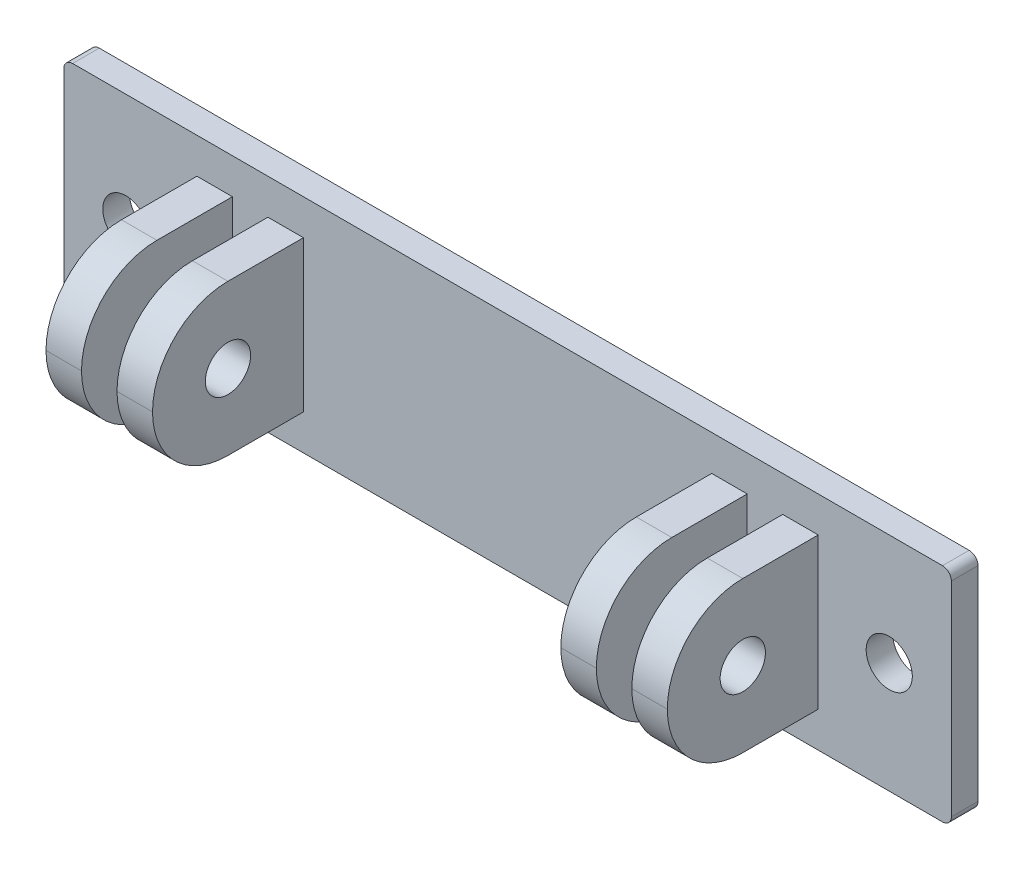
SolidWorks part; units mm, degrees
ref_plane "Ebene vorne" through (0, 0, 0) normal (0, 0, 1) x (1, 0, 0)
ref_plane "Ebene oben" through (0, 0, 0) normal (0, 1, 0) x (1, 0, 0)
ref_plane "Ebene rechts" through (0, 0, 0) normal (1, 0, 0) x (0, 0, -1)
sketch "Skizze1" plane through (0, 0, 0) normal (0, 0, 1) x (1, 0, 0)
  line L1 (95.9477, 18.6427) -> (-4.0523, 18.6427)
  line L2 (95.9477, 18.6427) -> (95.9477, -6.3573)
  line L3 (95.9477, -6.3573) -> (-4.0523, -6.3573)
  line L4 (-4.0523, 18.6427) -> (-4.0523, -6.3573)
  point P4 (-4.0523, -6.3573)
  dimension "D1" = 100
  dimension "D2" = 25
extrude "Aufsatz-Linear austragen1" add sketch "Skizze1" along normal blind 3 contours L2 L1 L4 L3
sketch "Skizze3" plane through (0, 0, 3) normal (0, 0, 1) x (1, 0, 0)
  line L1 (14.9477, 14.6427) -> (10.9477, 14.6427)
  line L2 (14.9477, 14.6427) -> (14.9477, -2.3573)
  line L3 (14.9477, -2.3573) -> (10.9477, -2.3573)
  line L4 (10.9477, 14.6427) -> (10.9477, -2.3573)
  line L6 (-42.759, -2.3573) -> (-24.1476, -2.3573) construction
  line L7 (18.9477, 14.6427) -> (22.9477, 14.6427)
  line L8 (18.9477, 14.6427) -> (18.9477, -2.3573)
  line L9 (18.9477, -2.3573) -> (22.9477, -2.3573)
  line L10 (22.9477, 14.6427) -> (22.9477, -2.3573)
  line L11 (-42.759, 14.6427) -> (-23.1415, 14.6427) construction
  line L12 (95.9477, -6.3573) -> (-4.0523, -6.3573) construction
  line L13 (95.9477, 18.6427) -> (-4.0523, 18.6427) construction
  line L14 (-4.0523, 18.6427) -> (-4.0523, -6.3573) construction
  line L15 (45.9477, 29.1139) -> (45.9477, -21.9394) construction
  line L16 (76.9477, -2.3573) -> (80.9477, -2.3573)
  line L17 (80.9477, 14.6427) -> (80.9477, -2.3573)
  line L18 (76.9477, 14.6427) -> (80.9477, 14.6427)
  line L19 (76.9477, 14.6427) -> (76.9477, -2.3573)
  line L20 (72.9477, -2.3573) -> (68.9477, -2.3573)
  line L21 (68.9477, 14.6427) -> (68.9477, -2.3573)
  line L22 (72.9477, 14.6427) -> (68.9477, 14.6427)
  line L23 (72.9477, 14.6427) -> (72.9477, -2.3573)
  line L24 (16.9477, 24.0473) -> (16.9477, -19.1688) construction
  line L25 (74.9477, 24.0473) -> (74.9477, -19.1688) construction
  line L26 (-4.0523, 18.6427) -> (-4.0523, -6.3573) construction
  line L27 (95.9477, 18.6427) -> (95.9477, -6.3573) construction
  line L28 (95.9477, 18.6427) -> (-4.0523, 18.6427) construction
  dimension "D1" = 4
  dimension "D2" = 4
  dimension "D3" = 4
  dimension "D4" = 4
  dimension "D5" = 4
  dimension "D6" = 15
  dimension "D7" = 50
  dimension "D8" = 2
  dimension "D9" = 2
  dimension "D10" = 58
extrude "Aufsatz-Linear austragen2" add sketch "Skizze3" along normal blind 17 contours L2 L1 L4 L3 | L8 L7 L10 L9 | L20 L21 L22 L23 | L16 L17 L18 L19
sketch "Skizze5" plane through (22.9477, 0, 0) normal (1, 0, 0) x (0, 0, -1)
  line L0 (-20, 14.6427) -> (-3, 14.6427) construction
  line L3 (-20, -2.3573) -> (-20, 14.6427) construction
  circle A0 centre (-11.5, 6.1427) radius 2.55
  circle A1 centre (-11.5, 6.1427) radius 8.5 construction
  dimension "D3" = 5.1
  dimension "D4" = 17
  dimension "D1" = 8.5
  dimension "D2" = 8.5
extrude "Schnitt-Linear austragen1" cut sketch "Skizze5" against normal through all both and the other way through all
fillet "Verrundung1" radius 8.5 8 edges at (20.9477, 14.6427, 20) (12.9477, 14.6427, 20) (12.9477, -2.3573, 20) (20.9477, -2.3573, 20) (78.9477, 14.6427, 20) (70.9477, 14.6427, 20) (70.9477, -2.3573, 20) (78.9477, -2.3573, 20)
sketch "Skizze6" plane through (0, 0, 3) normal (0, 0, 1) x (1, 0, 0)
  line L0 (45.9477, 26.6943) -> (45.9477, -13.9059) construction
  line L1 (-4.0523, 18.6427) -> (-4.0523, -6.3573) construction
  line L2 (-13.0483, 6.1427) -> (115.004, 6.1427) construction
  line L3 (95.9477, 18.6427) -> (-4.0523, 18.6427) construction
  circle A0 centre (2.9477, 6.1427) radius 2.6
  circle A1 centre (88.9477, 6.1427) radius 2.6
  dimension "D4" = 5.2
  dimension "D1" = 50
  dimension "D2" = 12.5
  dimension "D3" = 7
extrude "Schnitt-Linear austragen2" cut sketch "Skizze6" against normal blind 3
fillet "Verrundung2" radius 1 4 edges at (-4.0523, 18.6427, 1.5) (95.9477, 18.6427, 1.5) (95.9477, -6.3573, 1.5) (-4.0523, -6.3573, 1.5)
